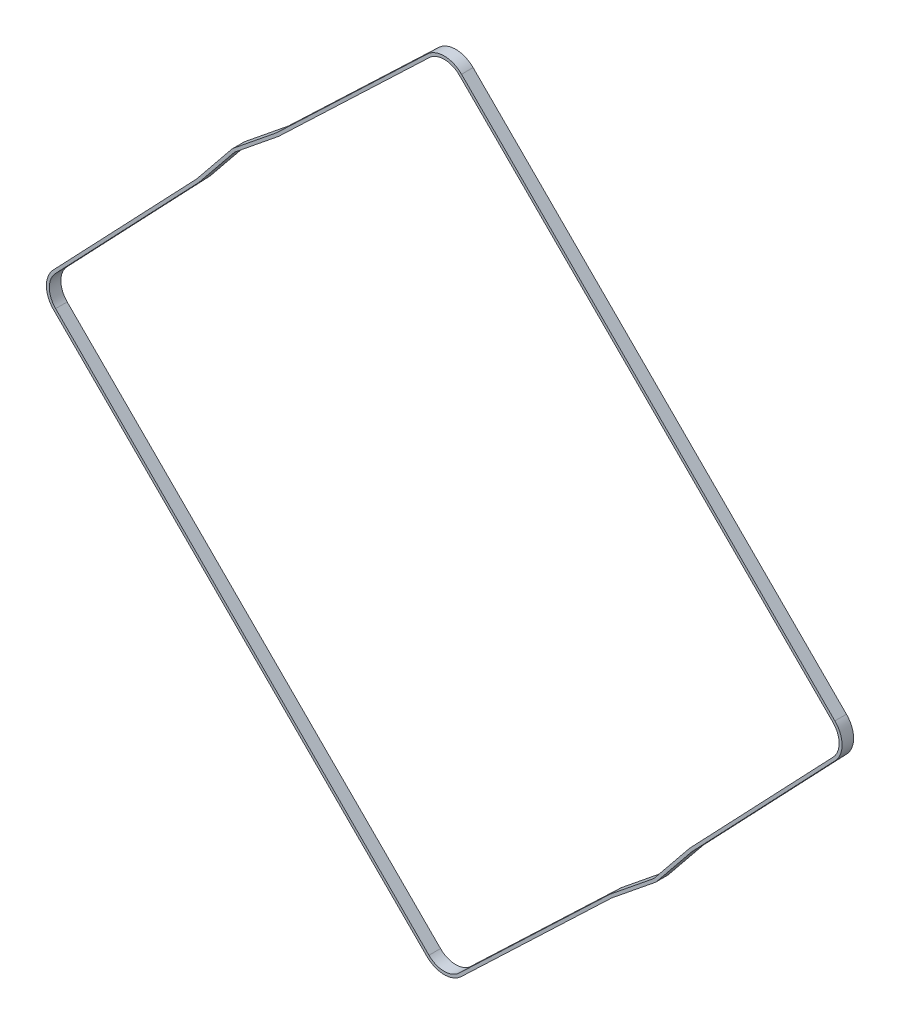
SolidWorks part; units mm, degrees
material "NEOPRENE"
ref_plane "Front Plane" through (0, 0, 0) normal (0, 0, 1) x (1, 0, 0)
ref_plane "Top Plane" through (0, 0, 0) normal (0, 1, 0) x (1, 0, 0)
ref_plane "Right Plane" through (0, 0, 0) normal (1, 0, 0) x (0, 0, -1)
sketch "Sketch2" plane through (0, 0, 0) normal (0, 0, 1) x (1, 0, 0)
  line L0 (0, 0) -> (1, 0) construction
  line L1 (0, 0) -> (0, 1) construction
  line L38 (-86.4158, -66.7842) -> (-108.5059, -84.6717)
  line L39 (-109.3283, -85.4941) -> (-127.2158, -107.5842)
  line L42 (86.4158, -321.2158) -> (108.5059, -303.3283)
  line L43 (109.3283, -302.5059) -> (127.2158, -280.4158)
  line L45 (-7.7349, 8.1196) -> (-85.7509, -66.2001)
  line L46 (-127.7999, -108.2491) -> (-202.1196, -186.2651)
  line L47 (7.7349, -396.1196) -> (85.7509, -321.7999)
  line L48 (127.7999, -279.7509) -> (202.1196, -201.7349)
  line L49 (-201.9296, -201.9296) -> (-7.9296, -395.9296)
  line L50 (201.9296, -186.0704) -> (7.9296, 7.9296)
  arc A1 (7.9296, 7.9296) -> (-7.7349, 8.1196) centre (0, 0) ccw
  arc A4 (-202.1196, -186.2651) -> (-201.9296, -201.9296) centre (-194, -194) ccw
  arc A10 (-7.9296, -395.9296) -> (7.7349, -396.1196) centre (0, -388) ccw
  arc A13 (202.1196, -201.7349) -> (201.9296, -186.0704) centre (194, -194) ccw
  arc A18 (-85.7509, -66.2001) -> (-86.4158, -66.7842) centre (-93.3381, -58.2355) cw
  arc A19 (-108.5059, -84.6717) -> (-109.3283, -85.4941) centre (-105.0054, -88.9946) ccw
  arc A20 (-127.2158, -107.5842) -> (-127.7999, -108.2491) centre (-135.7645, -100.6619) cw
  arc A21 (85.7509, -321.7999) -> (86.4158, -321.2158) centre (93.3381, -329.7645) cw
  arc A22 (108.5059, -303.3283) -> (109.3283, -302.5059) centre (105.0054, -299.0054) ccw
  arc A23 (127.2158, -280.4158) -> (127.7999, -279.7509) centre (135.7645, -287.3381) cw
extrude "Extrude-Thin1" add sketch "Sketch2" along normal blind 6 thin thin type one direction wall 1.52
